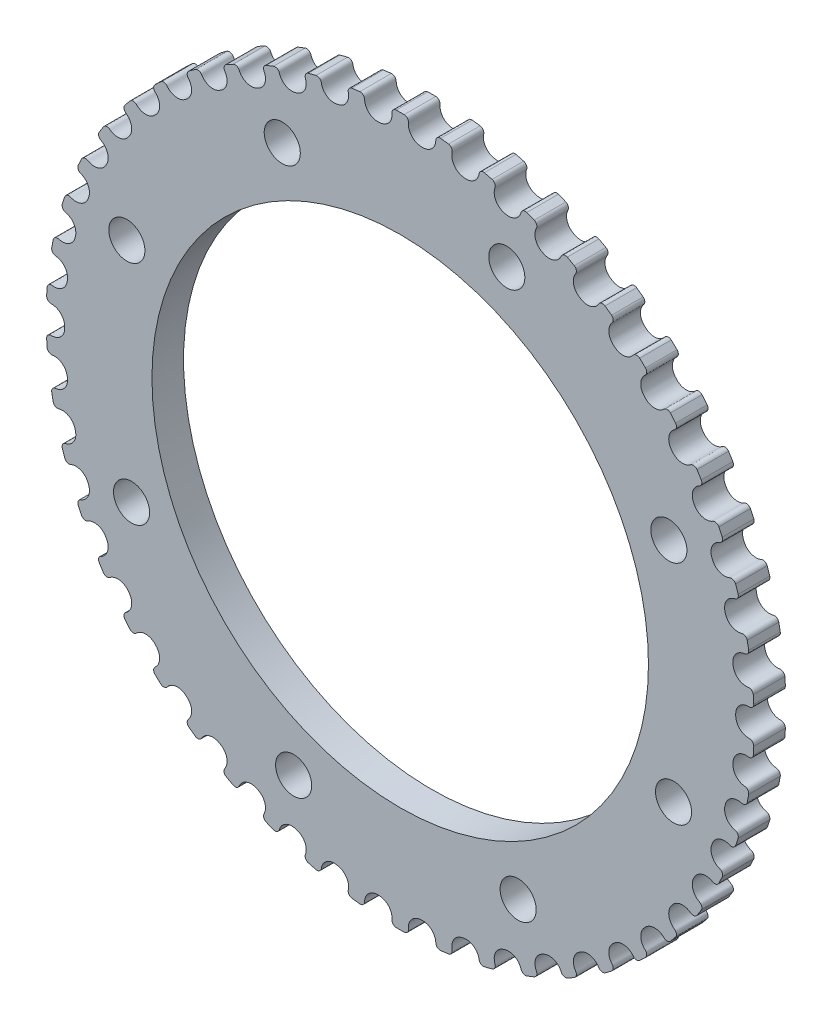
SolidWorks part; units mm, degrees
material "Thornel Mat VMA"
ref_plane "Front Plane" through (0, 0, 0) normal (0, 0, 1) x (1, 0, 0)
ref_plane "Top Plane" through (0, 0, 0) normal (0, 1, 0) x (1, 0, 0)
ref_plane "Right Plane" through (0, 0, 0) normal (1, 0, 0) x (0, 0, -1)
ref_axis "Axis1" through (0, 0, 55) along (0, 0, -1)
sketch "SketchRevolveGearBelt01" plane through (0, 0, 0) normal (1, 0, 0) x (0, 0, -1)
  line L0 (0, 0) -> (1, 0) construction
  line L1 (1.75, 0) -> (1.75, 39.2172)
  line L2 (1.75, 39.2172) -> (-1.75, 39.2172)
  line L3 (-1.75, 39.2172) -> (-1.75, 0)
  line L4 (-1.75, 0) -> (1.75, 0)
  dimension "GearBeltSide1" = 1.75
  dimension "GearBeltOutsideDiameter" = 39.2172
  dimension "GearBeltSide2" = 1.75
revolve "GearBelt01" add sketch "SketchRevolveGearBelt01" angle 360 about L0
sketch "SketchToothGearBelt01" plane through (0, 0, 0) normal (0, 0, 1) x (1, 0, 0)
  arc A0 (39.1647, 2.0323) -> (39.1647, -2.0323) centre (0, 0) cw
  spline S0 degree 3 poles (39.1647, -2.0323) (39.166, -2.006) (39.1649, -1.9663) (39.1569, -1.9141) (39.1478, -1.8755) (39.1356, -1.8378) (39.1204, -1.8013) (39.1023, -1.7661) (39.0814, -1.7324) (39.0578, -1.7006) (39.0317, -1.6708) (39.0033, -1.6432) (38.9728, -1.618) (38.9403, -1.5953) (38.9061, -1.5754) (38.8703, -1.5582) (38.8333, -1.5441) (38.7953, -1.533) (38.7565, -1.525) (38.7172, -1.5201) (38.6658, -1.5185) (38.59, -1.5198) (38.4897, -1.516) (38.3775, -1.5026) (38.2667, -1.4805) (38.158, -1.4498) (38.052, -1.4107) (37.9494, -1.3633) (37.8509, -1.3081) (37.7569, -1.2453) (37.6682, -1.1753) (37.5853, -1.0986) (37.5086, -1.0156) (37.4387, -0.9268) (37.376, -0.8329) (37.3208, -0.7343) (37.2735, -0.6317) (37.2344, -0.5257) (37.2037, -0.4169) (37.1817, -0.3061) (37.1683, -0.1939) (37.1652, -0.1051) (37.1655, -0.0405) (37.1655, 0) (37.1655, 0.0405) (37.1652, 0.1051) (37.1683, 0.1939) (37.1817, 0.3061) (37.2037, 0.4169) (37.2344, 0.5257) (37.2735, 0.6317) (37.3208, 0.7343) (37.376, 0.8329) (37.4387, 0.9268) (37.5086, 1.0156) (37.5853, 1.0986) (37.6682, 1.1753) (37.7569, 1.2453) (37.8509, 1.3081) (37.9494, 1.3633) (38.052, 1.4107) (38.158, 1.4498) (38.2667, 1.4805) (38.3775, 1.5026) (38.4897, 1.516) (38.59, 1.5198) (38.6658, 1.5185) (38.7172, 1.5201) (38.7565, 1.525) (38.7953, 1.533) (38.8333, 1.5441) (38.8703, 1.5582) (38.9061, 1.5754) (38.9403, 1.5953) (38.9728, 1.618) (39.0033, 1.6432) (39.0317, 1.6708) (39.0578, 1.7006) (39.0814, 1.7324) (39.1023, 1.7661) (39.1204, 1.8013) (39.1356, 1.8378) (39.1478, 1.8755) (39.1569, 1.9141) (39.1649, 1.9663) (39.166, 2.006) (39.1647, 2.0323) knots 0 0 0 0 0.012346 0.01852 0.024693 0.030866 0.037039 0.043212 0.049386 0.055559 0.061732 0.067905 0.074078 0.080252 0.086425 0.092598 0.098771 0.104944 0.111118 0.117291 0.123464 0.135171 0.152781 0.17039 0.188 0.205609 0.223219 0.240828 0.258438 0.276048 0.293657 0.311267 0.328876 0.346486 0.364095 0.381705 0.399315 0.416924 0.434534 0.452143 0.469753 0.487362 0.493681 0.5 0.506319 0.512638 0.530247 0.547857 0.565466 0.583076 0.600685 0.618295 0.635905 0.653514 0.671124 0.688733 0.706343 0.723952 0.741562 0.759172 0.776781 0.794391 0.812 0.82961 0.847219 0.864829 0.876536 0.882709 0.888882 0.895056 0.901229 0.907402 0.913575 0.919748 0.925922 0.932095 0.938268 0.944441 0.950614 0.956788 0.962961 0.969134 0.975307 0.98148 0.987654 1 1 1 1
extrude "ToothExtrudeCutGearBelt01" cut sketch "SketchToothGearBelt01" against normal blind 7.239 and the other way blind 7.239
pattern_circular "PatternGearBelt01" count 50 every 7.2 about axis through (0, 0, 55) along (0, 0, -1) of "ToothExtrudeCutGearBelt01"
sketch "BoreRevolveSketch" plane through (0, 0, 0) normal (1, 0, 0) x (0, 0, -1)
  line L0 (0, 0) -> (1, 0) construction
  line L1 (-7.239, 0) -> (7.239, 0)
  line L2 (7.239, 0) -> (7.239, 27.5)
  line L3 (7.239, 27.5) -> (-7.239, 27.5)
  line L4 (-7.239, 27.5) -> (-7.239, 0)
  dimension "BoreSide1" = 7.239
  dimension "TaperSide1" = 27.5
  dimension "BoreSide2" = 7.239
  dimension "TaperSide2" = 27.5
revolve "BoreRevolveCut" cut sketch "BoreRevolveSketch" angle 360 about L0
sketch "AuxiliarySketchGearBelt01" plane through (0, 0, 0) normal (0, 0, 1) x (1, 0, 0)
  circle A0 centre (0, 0) radius 39.7887 construction
  dimension "PitchDiameter" = 79.5774
sketch "Sketch1" plane through (0, 0, 1.75) normal (0, 0, 1) x (1, 0, 0)
  circle A0 centre (11.8053, 30.2801) radius 2 construction
  circle A1 centre (29.7589, 13.0636) radius 2 construction
  circle A2 centre (30.2801, -11.8053) radius 2 construction
  circle A3 centre (13.0636, -29.7589) radius 2 construction
  circle A4 centre (-11.8053, -30.2801) radius 2 construction
  circle A5 centre (-29.7589, -13.0636) radius 2 construction
  circle A6 centre (-30.2801, 11.8053) radius 2 construction
  circle A7 centre (-13.0636, 29.7589) radius 2 construction
  circle A8 centre (11.8053, 30.2801) radius 2
  circle A9 centre (29.7589, 13.0636) radius 2
  circle A10 centre (30.2801, -11.8053) radius 2
  circle A11 centre (13.0636, -29.7589) radius 2
  circle A12 centre (-11.8053, -30.2801) radius 2
  circle A13 centre (-29.7589, -13.0636) radius 2
  circle A14 centre (-30.2801, 11.8053) radius 2
  circle A15 centre (-13.0636, 29.7589) radius 2
extrude "Cut-Extrude1" cut sketch "Sketch1" against normal blind 10
